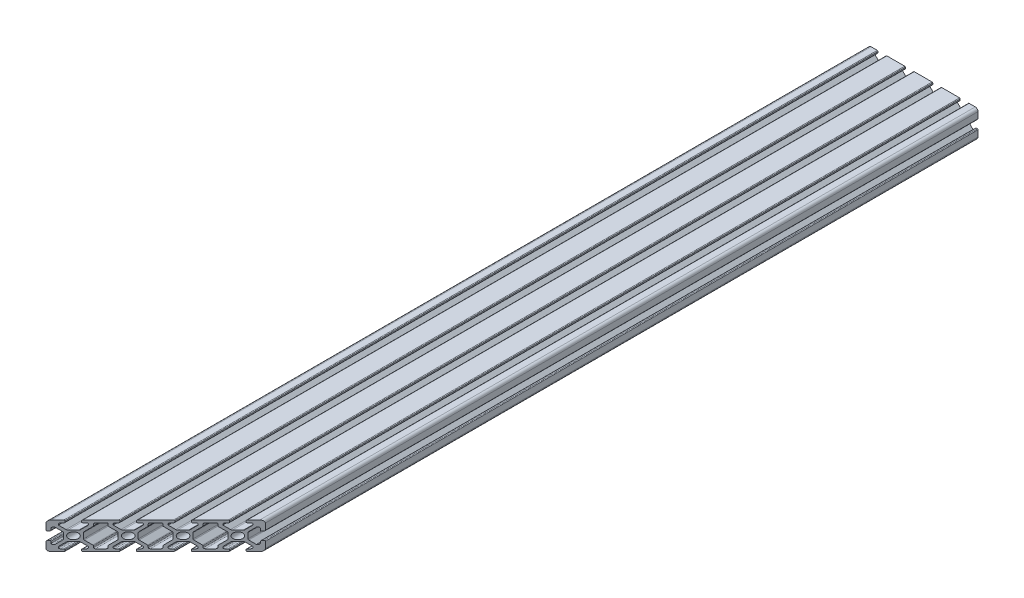
SolidWorks part; units mm, degrees
material "6063-T5"
ref_plane "Front Plane" through (0, 0, 0) normal (0, 0, 1) x (1, 0, 0)
ref_plane "Top Plane" through (0, 0, 0) normal (0, 1, 0) x (1, 0, 0)
ref_plane "Right Plane" through (0, 0, 0) normal (1, 0, 0) x (0, 0, -1)
sketch "Sketch1" plane through (0, 0, 0) normal (0, 0, 1) x (1, 0, 0)
  line L0 (2, 0) -> (6.5, 0)
  line L1 (80, 2) -> (80, 6.5)
  line L2 (78, 20) -> (73.5, 20)
  line L3 (0, 18) -> (0, 13.5)
  line L4 (33, 19.5) -> (33, 18.7)
  line L5 (27, 19.5) -> (27, 18.7)
  line L6 (7, 19.5) -> (7, 18.7)
  line L7 (13, 19.5) -> (13, 18.7)
  line L8 (6.5, 20) -> (2, 20)
  line L9 (53, 19.5) -> (53, 18.7)
  line L10 (47, 19.5) -> (47, 18.7)
  line L11 (73, 19.5) -> (73, 18.7)
  line L12 (67, 19.5) -> (67, 18.7)
  line L13 (33, 1.3) -> (33, 0.5)
  line L14 (27, 1.3) -> (27, 0.5)
  line L15 (53, 1.3) -> (53, 0.5)
  line L16 (47, 1.3) -> (47, 0.5)
  line L17 (73, 1.3) -> (73, 0.5)
  line L18 (67, 1.3) -> (67, 0.5)
  line L19 (13, 1.3) -> (13, 0.5)
  line L20 (7, 1.3) -> (7, 0.5)
  line L21 (13.5, 20) -> (26.5, 20) construction
  line L22 (26.5, 20) -> (13.5, 20)
  line L23 (46.5, 20) -> (33.5, 20)
  line L24 (66.5, 20) -> (53.5, 20)
  line L25 (73.5, 0) -> (78, 0)
  line L26 (53.5, 0) -> (66.5, 0)
  line L27 (33.5, 0) -> (46.5, 0)
  line L28 (13.5, 0) -> (26.5, 0)
  line L29 (79.5, 13) -> (78.7, 13)
  line L30 (79.5, 7) -> (78.7, 7)
  line L31 (0.5, 13) -> (1.3, 13)
  line L32 (0.5, 7) -> (1.3, 7)
  line L33 (0, 6.5) -> (0, 2)
  line L34 (80, 13.5) -> (80, 18)
  line L35 (1.8, 13.5) -> (1.8, 14.75)
  line L36 (5.25, 18.2) -> (6.5, 18.2)
  line L37 (78.2, 14.75) -> (78.2, 13.5)
  line L38 (74.75, 1.8) -> (73.5, 1.8)
  line L39 (1.8, 5.25) -> (1.8, 6.5)
  line L40 (13.5, 18.2) -> (14.75, 18.2)
  line L41 (6.5, 1.8) -> (5.25, 1.8)
  line L42 (33.5, 18.2) -> (34.75, 18.2)
  line L43 (26.5, 1.8) -> (25.25, 1.8)
  line L44 (53.5, 18.2) -> (54.75, 18.2)
  line L45 (46.5, 1.8) -> (45.25, 1.8)
  line L46 (73.5, 18.2) -> (74.75, 18.2)
  line L47 (66.5, 1.8) -> (65.25, 1.8)
  line L48 (78.2, 6.5) -> (78.2, 5.25)
  line L49 (12.6701, 13.9429) -> (15.5, 16.7728)
  line L50 (12.6701, 6.0571) -> (15.5, 3.2272)
  line L51 (32.6701, 13.9429) -> (35.5, 16.7728)
  line L52 (33.9429, 12.6701) -> (37.0803, 15.8075)
  line L53 (27.3299, 13.9429) -> (24.5, 16.7728)
  line L54 (22.9197, 15.8075) -> (26.0571, 12.6701)
  line L55 (27.3299, 6.0571) -> (24.5, 3.2272)
  line L56 (22.9197, 4.1925) -> (26.0571, 7.3299)
  line L57 (47.3299, 13.9429) -> (44.5, 16.7728)
  line L58 (42.9197, 15.8075) -> (46.0571, 12.6701)
  line L59 (47.3299, 6.0571) -> (44.5, 3.2272)
  line L60 (42.9197, 4.1925) -> (46.0571, 7.3299)
  line L61 (67.3299, 13.9429) -> (64.5, 16.7728)
  line L62 (62.9197, 15.8075) -> (66.0571, 12.6701)
  line L63 (67.3299, 6.0571) -> (64.5, 3.2272)
  line L64 (62.9197, 4.1925) -> (66.0571, 7.3299)
  line L65 (33.9429, 7.3299) -> (37.0803, 4.1925)
  line L66 (13.9429, 12.6701) -> (17.0803, 15.8075)
  line L67 (6.0571, 7.3299) -> (3.2272, 4.5)
  line L68 (7.3299, 6.0571) -> (4.5, 3.2272)
  line L69 (7.3299, 13.9429) -> (4.5, 16.7728)
  line L70 (32.6701, 6.0571) -> (35.5, 3.2272)
  line L71 (13.9429, 7.3299) -> (17.0803, 4.1925)
  line L72 (52.6701, 13.9429) -> (55.5, 16.7728)
  line L73 (6.0571, 12.6701) -> (3.2272, 15.5)
  line L74 (53.9429, 12.6701) -> (57.0803, 15.8075)
  line L75 (53.9429, 7.3299) -> (57.0803, 4.1925)
  line L76 (52.6701, 6.0571) -> (55.5, 3.2272)
  line L77 (72.6701, 13.9429) -> (75.5, 16.7728)
  line L78 (73.9429, 12.6701) -> (76.7728, 15.5)
  line L79 (73.9429, 7.3299) -> (76.7728, 4.5)
  line L80 (72.6701, 6.0571) -> (75.5, 3.2272)
  line L81 (28.037, 13.65) -> (31.963, 13.65)
  line L82 (18.05, 18.2) -> (21.95, 18.2)
  line L83 (14.75, 1.8) -> (13.5, 1.8)
  line L84 (15.5, 17.45) -> (15.5, 16.7728)
  line L85 (34.75, 1.8) -> (33.5, 1.8)
  line L86 (4.5, 17.45) -> (4.5, 16.7728)
  line L87 (54.75, 1.8) -> (53.5, 1.8)
  line L88 (24.5, 17.45) -> (24.5, 16.7728)
  line L89 (27.7144, 8.9872) -> (21.8, 3.0728) [skipped]
  line L90 (25.25, 18.2) -> (26.5, 18.2)
  line L91 (27.7144, 11.0128) -> (21.8, 16.9272) [skipped]
  line L92 (45.25, 18.2) -> (46.5, 18.2)
  line L93 (33.65, 11.963) -> (33.65, 8.037)
  line L94 (31.963, 6.35) -> (28.037, 6.35)
  line L95 (26.35, 8.037) -> (26.35, 11.963)
  line L96 (65.25, 18.2) -> (66.5, 18.2)
  line L97 (44.5, 17.45) -> (44.5, 16.7728)
  line L98 (35.5, 17.45) -> (35.5, 16.7728)
  line L99 (47.7144, 8.9872) -> (41.8, 3.0728) [skipped]
  line L100 (47.7144, 11.0128) -> (41.8, 16.9272) [skipped]
  line L101 (67.7144, 11.0128) -> (61.8, 16.9272) [skipped]
  line L102 (67.7144, 8.9872) -> (61.8, 3.0728) [skipped]
  line L103 (13.65, 11.963) -> (13.65, 8.037)
  line L104 (11.963, 6.35) -> (8.037, 6.35)
  line L105 (6.35, 8.037) -> (6.35, 11.963)
  line L106 (8.037, 13.65) -> (11.963, 13.65)
  line L107 (48.037, 13.65) -> (51.963, 13.65)
  line L108 (53.65, 11.963) -> (53.65, 8.037)
  line L109 (51.963, 6.35) -> (48.037, 6.35)
  line L110 (46.35, 8.037) -> (46.35, 11.963)
  line L111 (68.037, 13.65) -> (71.963, 13.65)
  line L112 (73.65, 11.963) -> (73.65, 8.037)
  line L113 (71.963, 6.35) -> (68.037, 6.35)
  line L114 (66.35, 8.037) -> (66.35, 11.963)
  line L115 (64.5, 17.45) -> (64.5, 16.7728)
  line L116 (55.5, 17.45) -> (55.5, 16.7728)
  line L117 (4.5, 2.55) -> (4.5, 3.2272)
  line L118 (75.5, 17.45) -> (75.5, 16.7728)
  line L119 (24.5, 2.55) -> (24.5, 3.2272)
  line L120 (15.5, 2.55) -> (15.5, 3.2272)
  line L121 (44.5, 2.55) -> (44.5, 3.2272)
  line L122 (35.5, 2.55) -> (35.5, 3.2272)
  line L123 (64.5, 2.55) -> (64.5, 3.2272)
  line L124 (55.5, 2.55) -> (55.5, 3.2272)
  line L125 (2.55, 15.5) -> (3.2272, 15.5)
  line L126 (75.5, 2.55) -> (75.5, 3.2272)
  line L127 (2.55, 4.5) -> (3.2272, 4.5)
  line L128 (77.45, 15.5) -> (76.7728, 15.5)
  line L129 (17.3, 17.45) -> (17.3, 16.3379)
  line L130 (77.45, 4.5) -> (76.7728, 4.5)
  line L131 (22.7, 17.45) -> (22.7, 16.3379)
  line L132 (38.05, 18.2) -> (41.95, 18.2)
  line L133 (37.3, 17.45) -> (37.3, 16.3379)
  line L134 (42.7, 17.45) -> (42.7, 16.3379)
  line L135 (58.05, 18.2) -> (61.95, 18.2)
  line L136 (57.3, 17.45) -> (57.3, 16.3379)
  line L137 (62.7, 17.45) -> (62.7, 16.3379)
  line L138 (17.3, 3.6621) -> (17.3, 2.55)
  line L139 (18.05, 1.8) -> (21.95, 1.8)
  line L140 (22.7, 2.55) -> (22.7, 3.6621)
  line L141 (37.3, 3.6621) -> (37.3, 2.55)
  line L142 (38.05, 1.8) -> (41.95, 1.8)
  line L143 (42.7, 2.55) -> (42.7, 3.6621)
  line L144 (57.3, 3.6621) -> (57.3, 2.55)
  line L145 (58.05, 1.8) -> (61.95, 1.8)
  line L146 (62.7, 2.55) -> (62.7, 3.6621)
  circle A0 centre (10, 10) radius 2.5
  circle A1 centre (30, 10) radius 2.5
  circle A2 centre (50, 10) radius 2.5
  circle A3 centre (70, 10) radius 2.5
  arc A4 (78, 0) -> (80, 2) centre (78, 2) ccw
  arc A5 (80, 18) -> (78, 20) centre (78, 18) ccw
  arc A6 (2, 0) -> (0, 2) centre (2, 2) cw
  arc A7 (2, 20) -> (0, 18) centre (2, 18) ccw
  arc A8 (12.6701, 13.9429) -> (11.963, 13.65) centre (11.963, 14.65) cw
  arc A9 (7.3299, 13.9429) -> (8.037, 13.65) centre (8.037, 14.65) ccw
  arc A10 (6.0571, 12.6701) -> (6.35, 11.963) centre (5.35, 11.963) cw
  arc A11 (6.0571, 7.3299) -> (6.35, 8.037) centre (5.35, 8.037) ccw
  arc A12 (7.3299, 6.0571) -> (8.037, 6.35) centre (8.037, 5.35) cw
  arc A13 (12.6701, 6.0571) -> (11.963, 6.35) centre (11.963, 5.35) ccw
  arc A14 (32.6701, 6.0571) -> (31.963, 6.35) centre (31.963, 5.35) ccw
  arc A15 (27.3299, 6.0571) -> (28.037, 6.35) centre (28.037, 5.35) cw
  arc A16 (27.3299, 13.9429) -> (28.037, 13.65) centre (28.037, 14.65) ccw
  arc A17 (32.6701, 13.9429) -> (31.963, 13.65) centre (31.963, 14.65) cw
  arc A18 (47.3299, 6.0571) -> (48.037, 6.35) centre (48.037, 5.35) cw
  arc A19 (52.6701, 6.0571) -> (51.963, 6.35) centre (51.963, 5.35) ccw
  arc A20 (52.6701, 13.9429) -> (51.963, 13.65) centre (51.963, 14.65) cw
  arc A21 (47.3299, 13.9429) -> (48.037, 13.65) centre (48.037, 14.65) ccw
  arc A22 (72.6701, 13.9429) -> (71.963, 13.65) centre (71.963, 14.65) cw
  arc A23 (67.3299, 13.9429) -> (68.037, 13.65) centre (68.037, 14.65) ccw
  arc A24 (67.3299, 6.0571) -> (68.037, 6.35) centre (68.037, 5.35) cw
  arc A25 (72.6701, 6.0571) -> (71.963, 6.35) centre (71.963, 5.35) ccw
  arc A26 (73.9429, 7.3299) -> (73.65, 8.037) centre (74.65, 8.037) cw
  arc A27 (73.9429, 12.6701) -> (73.65, 11.963) centre (74.65, 11.963) ccw
  arc A28 (66.0571, 7.3299) -> (66.35, 8.037) centre (65.35, 8.037) ccw
  arc A29 (66.0571, 12.6701) -> (66.35, 11.963) centre (65.35, 11.963) cw
  arc A30 (53.9429, 7.3299) -> (53.65, 8.037) centre (54.65, 8.037) cw
  arc A31 (53.9429, 12.6701) -> (53.65, 11.963) centre (54.65, 11.963) ccw
  arc A32 (78.2, 14.75) -> (77.45, 15.5) centre (77.45, 14.75) ccw
  arc A33 (75.5, 17.45) -> (74.75, 18.2) centre (74.75, 17.45) ccw
  arc A34 (78.2, 5.25) -> (77.45, 4.5) centre (77.45, 5.25) cw
  arc A35 (75.5, 2.55) -> (74.75, 1.8) centre (74.75, 2.55) cw
  arc A36 (46.0571, 7.3299) -> (46.35, 8.037) centre (45.35, 8.037) ccw
  arc A37 (46.0571, 12.6701) -> (46.35, 11.963) centre (45.35, 11.963) cw
  arc A38 (33.9429, 7.3299) -> (33.65, 8.037) centre (34.65, 8.037) cw
  arc A39 (33.9429, 12.6701) -> (33.65, 11.963) centre (34.65, 11.963) ccw
  arc A40 (13.9429, 12.6701) -> (13.65, 11.963) centre (14.65, 11.963) ccw
  arc A41 (13.9429, 7.3299) -> (13.65, 8.037) centre (14.65, 8.037) cw
  arc A42 (26.0571, 7.3299) -> (26.35, 8.037) centre (25.35, 8.037) ccw
  arc A43 (26.0571, 12.6701) -> (26.35, 11.963) centre (25.35, 11.963) cw
  arc A44 (65.25, 1.8) -> (64.5, 2.55) centre (65.25, 2.55) cw
  arc A45 (61.95, 1.8) -> (62.7, 2.55) centre (61.95, 2.55) ccw
  arc A46 (57.3, 2.55) -> (58.05, 1.8) centre (58.05, 2.55) ccw
  arc A47 (54.75, 1.8) -> (55.5, 2.55) centre (54.75, 2.55) ccw
  arc A48 (45.25, 1.8) -> (44.5, 2.55) centre (45.25, 2.55) cw
  arc A49 (64.5, 17.45) -> (65.25, 18.2) centre (65.25, 17.45) cw
  arc A50 (61.95, 18.2) -> (62.7, 17.45) centre (61.95, 17.45) cw
  arc A51 (58.05, 18.2) -> (57.3, 17.45) centre (58.05, 17.45) ccw
  arc A52 (53, 18.7) -> (53.5, 18.2) centre (53.5, 18.7) ccw
  arc A53 (53, 19.5) -> (53.5, 20) centre (53.5, 19.5) cw
  arc A54 (67, 18.7) -> (66.5, 18.2) centre (66.5, 18.7) cw
  arc A55 (67, 19.5) -> (66.5, 20) centre (66.5, 19.5) ccw
  arc A56 (73, 18.7) -> (73.5, 18.2) centre (73.5, 18.7) ccw
  arc A57 (73, 19.5) -> (73.5, 20) centre (73.5, 19.5) cw
  arc A58 (78.7, 13) -> (78.2, 13.5) centre (78.7, 13.5) cw
  arc A59 (79.5, 13) -> (80, 13.5) centre (79.5, 13.5) ccw
  arc A60 (78.7, 7) -> (78.2, 6.5) centre (78.7, 6.5) ccw
  arc A61 (79.5, 7) -> (80, 6.5) centre (79.5, 6.5) cw
  arc A62 (73, 0.5) -> (73.5, 0) centre (73.5, 0.5) ccw
  arc A63 (73, 1.3) -> (73.5, 1.8) centre (73.5, 1.3) cw
  arc A64 (67, 0.5) -> (66.5, 0) centre (66.5, 0.5) cw
  arc A65 (67, 1.3) -> (66.5, 1.8) centre (66.5, 1.3) ccw
  arc A66 (53, 0.5) -> (53.5, 0) centre (53.5, 0.5) ccw
  arc A67 (53, 1.3) -> (53.5, 1.8) centre (53.5, 1.3) cw
  arc A68 (47, 0.5) -> (46.5, 0) centre (46.5, 0.5) cw
  arc A69 (47, 1.3) -> (46.5, 1.8) centre (46.5, 1.3) ccw
  arc A70 (33, 0.5) -> (33.5, 0) centre (33.5, 0.5) ccw
  arc A71 (33, 1.3) -> (33.5, 1.8) centre (33.5, 1.3) cw
  arc A72 (27, 0.5) -> (26.5, 0) centre (26.5, 0.5) cw
  arc A73 (27, 1.3) -> (26.5, 1.8) centre (26.5, 1.3) ccw
  arc A74 (47, 18.7) -> (46.5, 18.2) centre (46.5, 18.7) cw
  arc A75 (47, 19.5) -> (46.5, 20) centre (46.5, 19.5) ccw
  arc A76 (33, 18.7) -> (33.5, 18.2) centre (33.5, 18.7) ccw
  arc A77 (33, 19.5) -> (33.5, 20) centre (33.5, 19.5) cw
  arc A78 (27, 18.7) -> (26.5, 18.2) centre (26.5, 18.7) cw
  arc A79 (27, 19.5) -> (26.5, 20) centre (26.5, 19.5) ccw
  arc A80 (13, 18.7) -> (13.5, 18.2) centre (13.5, 18.7) ccw
  arc A81 (13.5, 20) -> (13, 19.5) centre (13.5, 19.5) ccw
  arc A82 (13, 0.5) -> (13.5, 0) centre (13.5, 0.5) ccw
  arc A83 (13, 1.3) -> (13.5, 1.8) centre (13.5, 1.3) cw
  arc A84 (7, 0.5) -> (6.5, 0) centre (6.5, 0.5) cw
  arc A85 (7, 1.3) -> (6.5, 1.8) centre (6.5, 1.3) ccw
  arc A86 (0, 6.5) -> (0.5, 7) centre (0.5, 6.5) cw
  arc A87 (1.3, 7) -> (1.8, 6.5) centre (1.3, 6.5) cw
  arc A88 (0, 13.5) -> (0.5, 13) centre (0.5, 13.5) ccw
  arc A89 (1.3, 13) -> (1.8, 13.5) centre (1.3, 13.5) ccw
  arc A90 (6.5, 20) -> (7, 19.5) centre (6.5, 19.5) cw
  arc A91 (7, 18.7) -> (6.5, 18.2) centre (6.5, 18.7) cw
  arc A92 (55.5, 17.45) -> (54.75, 18.2) centre (54.75, 17.45) ccw
  arc A93 (44.5, 17.45) -> (45.25, 18.2) centre (45.25, 17.45) cw
  arc A94 (37.3, 2.55) -> (38.05, 1.8) centre (38.05, 2.55) ccw
  arc A95 (38.05, 18.2) -> (37.3, 17.45) centre (38.05, 17.45) ccw
  arc A96 (41.95, 18.2) -> (42.7, 17.45) centre (41.95, 17.45) cw
  arc A97 (41.95, 1.8) -> (42.7, 2.55) centre (41.95, 2.55) ccw
  arc A98 (34.75, 1.8) -> (35.5, 2.55) centre (34.75, 2.55) ccw
  arc A99 (25.25, 1.8) -> (24.5, 2.55) centre (25.25, 2.55) cw
  arc A100 (14.75, 1.8) -> (15.5, 2.55) centre (14.75, 2.55) ccw
  arc A101 (5.25, 1.8) -> (4.5, 2.55) centre (5.25, 2.55) cw
  arc A102 (2.55, 4.5) -> (1.8, 5.25) centre (2.55, 5.25) cw
  arc A103 (1.8, 14.75) -> (2.55, 15.5) centre (2.55, 14.75) cw
  arc A104 (24.5, 17.45) -> (25.25, 18.2) centre (25.25, 17.45) cw
  arc A105 (34.75, 18.2) -> (35.5, 17.45) centre (34.75, 17.45) cw
  arc A106 (21.95, 18.2) -> (22.7, 17.45) centre (21.95, 17.45) cw
  arc A107 (18.05, 18.2) -> (17.3, 17.45) centre (18.05, 17.45) ccw
  arc A108 (15.5, 17.45) -> (14.75, 18.2) centre (14.75, 17.45) ccw
  arc A109 (5.25, 18.2) -> (4.5, 17.45) centre (5.25, 17.45) ccw
  arc A110 (62.7, 3.6621) -> (62.9197, 4.1925) centre (63.45, 3.6621) cw
  arc A111 (57.3, 3.6621) -> (57.0803, 4.1925) centre (56.55, 3.6621) ccw
  arc A112 (62.7, 16.3379) -> (62.9197, 15.8075) centre (63.45, 16.3379) ccw
  arc A113 (57.3, 16.3379) -> (57.0803, 15.8075) centre (56.55, 16.3379) cw
  arc A114 (42.7, 3.6621) -> (42.9197, 4.1925) centre (43.45, 3.6621) cw
  arc A115 (37.3, 3.6621) -> (37.0803, 4.1925) centre (36.55, 3.6621) ccw
  arc A116 (42.7, 16.3379) -> (42.9197, 15.8075) centre (43.45, 16.3379) ccw
  arc A117 (37.3, 16.3379) -> (37.0803, 15.8075) centre (36.55, 16.3379) cw
  arc A118 (22.7, 16.3379) -> (22.9197, 15.8075) centre (23.45, 16.3379) ccw
  arc A119 (17.3, 16.3379) -> (17.0803, 15.8075) centre (16.55, 16.3379) cw
  arc A120 (17.3, 3.6621) -> (17.0803, 4.1925) centre (16.55, 3.6621) ccw
  arc A121 (22.7, 3.6621) -> (22.9197, 4.1925) centre (23.45, 3.6621) cw
  arc A122 (21.95, 1.8) -> (22.7, 2.55) centre (21.95, 2.55) ccw
  arc A123 (17.3, 2.55) -> (18.05, 1.8) centre (18.05, 2.55) ccw
  point P124 (0, 0)
  point P394 (17.3, 16.0272)
  dimension "D1" = 4
  dimension "D3" = 4
  dimension "D2" = 2
  dimension "D4" = 3
extrude "Boss-Extrude1" add sketch "Sketch1" along normal mid plane 600
sketch "Sketch2" plane through (0, 20, 0) normal (0, 1, 0) x (1, 0, 0)
  line L0 (0, -300) -> (80, -220)
  line L1 (80, -300) -> (80, 300) construction
  line L2 (80, -220) -> (80, -300)
  line L3 (80, -300) -> (0, -300)
  dimension "D1" = 45
extrude "Cut-Extrude1" cut sketch "Sketch2" against normal through all
